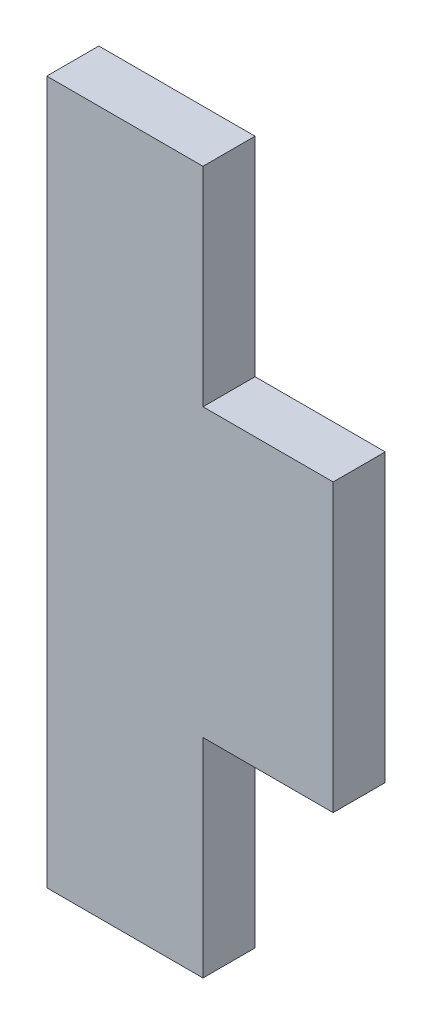
SolidWorks part; units mm, degrees
ref_plane "Front Plane" through (0, 0, 0) normal (0, 0, 1) x (1, 0, 0)
ref_plane "Top Plane" through (0, 0, 0) normal (0, 1, 0) x (1, 0, 0)
ref_plane "Right Plane" through (0, 0, 0) normal (1, 0, 0) x (0, 0, -1)
sketch "Sketch4" plane through (0, 0, 0) normal (0, 0, 1) x (1, 0, 0)
  line L0 (-31.9513, 58.173) -> (-1.9513, 58.173)
  line L9 (-31.9513, 58.173) -> (-31.9513, -76.827)
  line L10 (-1.9513, 58.173) -> (-1.9513, 18.173)
  line L11 (-1.9513, -76.827) -> (-31.9513, -76.827)
  line L12 (-1.9513, -76.827) -> (-1.9513, -36.827)
  line L13 (-1.9513, -36.827) -> (23.0487, -36.827)
  line L14 (23.0487, -36.827) -> (23.0487, 18.173)
  line L15 (23.0487, 18.173) -> (-1.9513, 18.173)
  dimension "D1" = 30
  dimension "D2" = 135
  dimension "D3" = 55
  dimension "D4" = 25
  dimension "D5" = 40
  dimension "D6" = 30
extrude "Boss-Extrude9" add sketch "Sketch4" along normal blind 10 contours L0 L10 L15 L14 L13 L12 L11 L9
